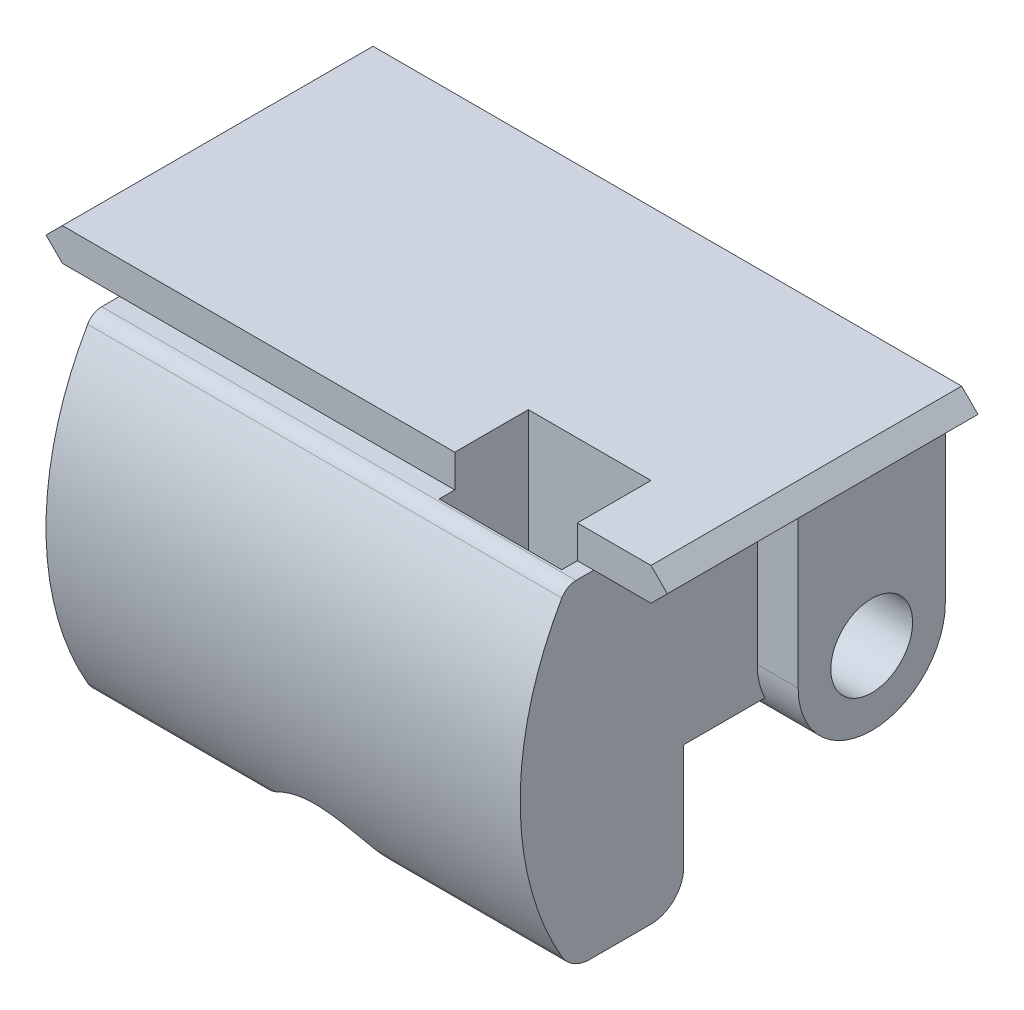
SolidWorks part; units mm, degrees
other "Markup1"
sketch "Sketch21" plane through (-21.59, 12.7, -5.715) normal (0, 1, 0) x (1, 0, 0)
sketch "Sketch23" plane through (-21.59, 12.7, -5.715) normal (0, 1, 0) x (1, 0, 0)
sketch "Sketch25" plane through (-24.13, 15.24, -5.715) normal (0, 1, 0) x (1, 0, 0)
sketch "Sketch26" plane through (-24.13, 15.24, -5.715) normal (0, 1, 0) x (1, 0, 0)
ref_plane "Front Plane" through (0, 0, 0) normal (0, 0, 1) x (1, 0, 0)
ref_plane "Top Plane" through (0, 0, 0) normal (0, 1, 0) x (1, 0, 0)
ref_plane "Right Plane" through (0, 0, 0) normal (1, 0, 0) x (0, 0, -1)
sketch "Sketch1" plane through (0, 0, 0) normal (1, 0, 0) x (0, 0, -1)
  circle A0 centre (0, 0) radius 5.715
  dimension "D1" = 11.43
extrude "Boss-Extrude1" add sketch "Sketch1" along normal blind 21.59 and the other way blind 21.59
sketch "Sketch2" plane through (0, 0, 0) normal (0, 0, 1) x (1, 0, 0)
  line L1 (-17.78, -3.175) -> (17.78, -3.175)
  line L2 (-17.78, -3.175) -> (-17.78, 8.255)
  line L3 (-17.78, 8.255) -> (17.78, 8.255)
  line L4 (17.78, -3.175) -> (17.78, 8.255)
  point P4 (0, 8.255)
  dimension "D1" = 35.56
  dimension "D2" = 11.43
  dimension "D3" = 2.54
sketch "Sketch3" plane through (0, 0, 0) normal (0, 1, 0) x (1, 0, 0)
  line L0 (21.59, -5.715) -> (21.59, 5.715) construction
  line L1 (-21.59, 5.715) -> (21.59, 5.715)
  line L2 (-21.59, 5.715) -> (-21.59, -5.715)
  line L3 (-21.59, -5.715) -> (21.59, -5.715)
  line L4 (21.59, 5.715) -> (21.59, -5.715)
  line L5 (-21.59, -5.715) -> (21.59, -5.715) construction
extrude "Boss-Extrude3" add sketch "Sketch3" along normal blind 12.7
sketch "Sketch4" plane through (0, 0, 0) normal (0, 0, 1) x (1, 0, 0)
  line L1 (-18.415, -2.54) -> (18.415, -2.54)
  line L2 (-18.415, -2.54) -> (-18.415, 12.7)
  line L3 (-18.415, 12.7) -> (18.415, 12.7)
  line L4 (18.415, -2.54) -> (18.415, 12.7)
  line L5 (-21.59, -5.715) -> (21.59, -5.715) construction
  line L6 (-21.59, 12.7) -> (21.59, 12.7) construction
  point P6 (0, -2.54)
  dimension "D2" = 36.83
  dimension "D3" = 3.175
extrude "Boss-Extrude4" add sketch "Sketch4" along normal blind 24.13
sketch "Sketch7" plane through (0, -2.54, 0) normal (0, -1, 0) x (1, 0, 0)
  line L0 (18.415, 24.13) -> (18.415, 0) construction
  line L1 (-18.415, 24.13) -> (18.415, 24.13)
  line L2 (-18.415, 24.13) -> (-18.415, 11.43)
  line L3 (-18.415, 11.43) -> (18.415, 11.43)
  line L4 (18.415, 24.13) -> (18.415, 11.43)
  dimension "D1" = 12.7
extrude "Boss-Extrude5" add sketch "Sketch7" along normal blind 10.795
sketch "Sketch5" plane through (-21.59, 0, 0) normal (-1, 0, 0) x (0, 0, 1)
  circle A0 centre (0, 0) radius 3.175
  dimension "D1" = 6.35
extrude "Cut-Extrude1" cut sketch "Sketch5" against normal through all
sketch "Sketch6" plane through (21.59, 0, 0) normal (1, 0, 0) x (0, 0, -1)
  line L0 (-19.4454, 14.2875) -> (-27.94, 14.2875)
  line L2 (-27.94, 14.2875) -> (-27.94, -14.2875)
  line L3 (-27.94, -14.2875) -> (-19.4454, -14.2875)
  circle A0 centre (0, 0) radius 24.13
  circle A1 centre (0, 0) radius 3.175 construction
  point P2 (-27.94, 0)
  dimension "D1" = 48.26
  dimension "D2" = 28.575
  dimension "D3" = 27.94
extrude "Cut-Extrude5" cut sketch "Sketch6" against normal through all contours A0 L0 L2 L3 region at (21.59, 0, 25.1095)
sketch "Sketch8" plane through (18.415, 0, 0) normal (1, 0, 0) x (0, 0, -1)
  circle A0 centre (0, 0) radius 14.2875 construction
  circle A1 centre (-14.2875, 0) radius 3.9688 construction
  dimension "D1" = 28.575
  dimension "D2" = 7.9375
fillet "Fillet1" radius 2.54 2 edges at (0, -13.335, 20.1106) (0, -13.335, 11.43)
sketch "Sketch10" plane through (0, 0, 0) normal (1, 0, 0) x (0, 0, -1)
  line L1 (-19.685, 5.08) -> (3.175, 5.08)
  line L2 (-19.685, 5.08) -> (-19.685, -20.32)
  line L3 (-19.685, -20.32) -> (3.175, -20.32)
  line L4 (3.175, 5.08) -> (3.175, -20.32)
  line L6 (5.715, 12.7) -> (5.715, 0) construction
  dimension "D4" = 2.54
  dimension "D1" = 5.08
  dimension "D2" = 22.86
  dimension "D3" = 25.4
extrude "Cut-Extrude6" cut sketch "Sketch10" against normal blind 6.35 and the other way blind 6.35
sketch "Sketch11" plane through (0, 0, 0) normal (1, 0, 0) x (0, 0, -1)
  circle A0 centre (-14.2875, 0) radius 1.778
  dimension "D1" = 3.556
extrude "Cut-Extrude7" cut sketch "Sketch11" against normal through all
combine bodies "Combine1" operation type add bodies to combine 112 111 114
ref_axis "Axis1" through (24.4475, 0, 0) along (-1, 0, 0)
sketch "Sketch24" plane through (0, 12.7, 0) normal (0, 1, 0) x (1, 0, 0)
  line L0 (21.59, 5.715) -> (-21.59, 5.715) construction
  line L1 (-24.13, 5.715) -> (24.13, 5.715)
  line L2 (-24.13, 5.715) -> (-24.13, -18.415)
  line L3 (-24.13, -18.415) -> (24.13, -18.415)
  line L4 (24.13, 5.715) -> (24.13, -18.415)
  line L6 (-21.59, 5.715) -> (-21.59, -5.715) construction
  dimension "D1" = 2.54
  dimension "D2" = 48.26
  dimension "D3" = 24.13
extrude "Boss-Extrude6" add sketch "Sketch24" along normal blind 2.54
ref_plane "Plane2" through (0, 0, 0) normal (0, 0.9848, 0.1736) x (-1, 0, 0)
ref_plane "Plane3" through (0, -10.0056, -1.7643) normal (0, 0.9848, 0.1736) x (-1, 0, 0)
sketch "Sketch17" plane through (0, -10.0056, -1.7643) normal (0, 0.9848, 0.1736) x (-1, 0, 0)
  line L0 (6.35, 21.6668) -> (-6.35, 21.6668)
  line L2 (6.35, 20.729) -> (18.415, 20.729) construction
  line L3 (6.35, 21.6668) -> (-6.35, 21.6668) construction
  line L5 (6.35, 21.6668) -> (-6.35, 21.6668)
  line L6 (6.35, 21.6668) -> (6.35, 18.4918)
  line L7 (6.35, 18.4918) -> (-6.35, 18.4918)
  line L8 (-6.35, 21.6668) -> (-6.35, 18.4918)
  circle A0 centre (0, 9.2234) radius 13.97
  dimension "D1" = 27.94
  dimension "D2" = 12.7
  dimension "D3" = 3.175
extrude "Cut-Extrude9" cut sketch "Sketch17" along normal blind 8.89 contours L0 A0 | L6 L5 L8 L7 region at (0, -13.8746, 20.1777)
sketch "Sketch18" plane through (0, -13.335, 0) normal (0, 1, 0) x (1, 0, 0)
  line L0 (6.35, -13.97) -> (6.35, -18.6975) construction
  line L1 (6.35, -11.43) -> (18.415, -11.43) construction
  line L3 (3.7712, -20.8972) -> (18.415, -20.8972) construction
  line L8 (7.62, -19.6272) -> (17.145, -19.6272)
  line L9 (7.62, -19.6272) -> (7.62, -12.7)
  line L10 (7.62, -12.7) -> (17.145, -12.7)
  line L11 (17.145, -19.6272) -> (17.145, -12.7)
  line L12 (7.62, -19.6272) -> (17.145, -12.7) construction
  line L13 (7.62, -12.7) -> (17.145, -19.6272) construction
  point P16 (12.3825, -16.1636)
  dimension "D1" = 1.27
  dimension "D2" = 9.525
  dimension "D3" = 1.27
  dimension "D4" = 1.27
extrude "Cut-Extrude13" cut sketch "Sketch18" along normal through all contours L8 L11 L10 L9
chamfer "Chamfer1" distance 1.27 4 edges at (24.13, 15.24, 6.35) (24.13, 12.7, 6.35) (-24.13, 15.24, 6.35) (-24.13, 12.7, 6.35)
fillet "Fillet2" radius 1.27 1 edges at (0, 12.7, 20.5175)
